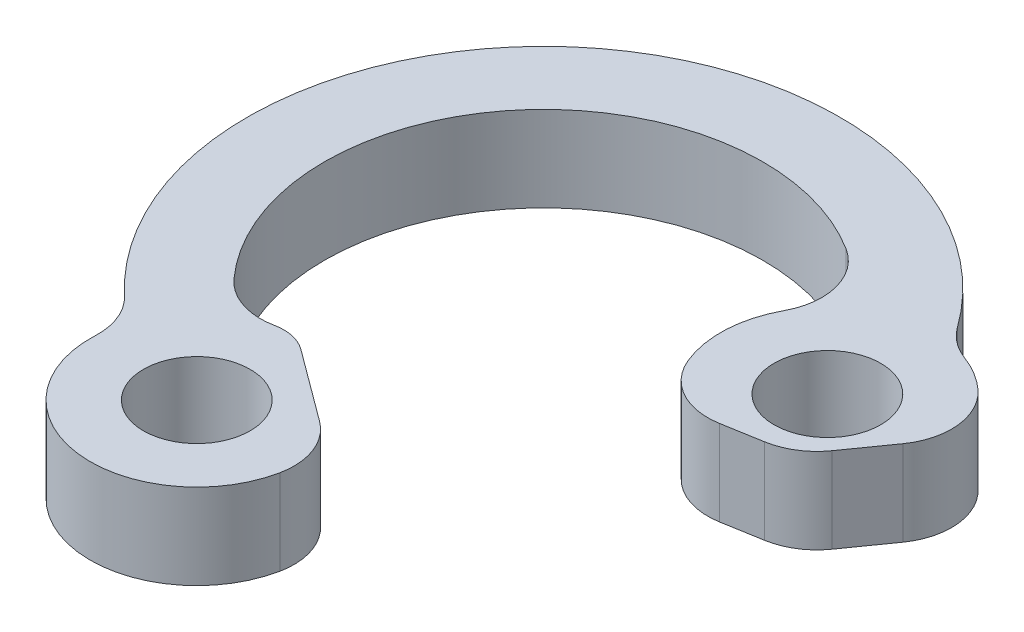
SolidWorks part; units mm, degrees
ref_plane "Front Plane" through (0, 0, 0) normal (0, 0, 1) x (1, 0, 0)
ref_plane "Top Plane" through (0, 0, 0) normal (0, 1, 0) x (1, 0, 0)
ref_plane "Right Plane" through (0, 0, 0) normal (1, 0, 0) x (0, 0, -1)
sketch "Sketch2" plane through (0, 0, 0) normal (0, 1, 0) x (1, 0, 0)
  circle A3 centre (87.0735, 81.0463) radius 2.5
  circle A5 centre (72.5387, 66.0204) radius 2.5
  arc A9 (84.158, 85.1082) -> (87.9596, 85.9672) centre (87.0735, 81.0463) ccw
  arc A10 (67.7859, 67.5732) -> (70.0824, 70.3755) centre (72.5387, 66.0204) ccw
  arc A16 (84.158, 85.1082) -> (70.0824, 70.3755) centre (76.1332, 78.6848) ccw
  arc A18 (87.9715, 85.965) -> (67.7859, 67.5732) centre (76.1332, 78.6848) ccw
extrude "Boss-Extrude1" add sketch "Sketch2" along normal blind 4 contours A18 A16 A3 A5 region at (68.387, 0, -86.0855)
fillet "Fillet1" radius 3 4 edges at (67.7859, 2, -67.5732) (70.0824, 2, -70.3755) (84.158, 2, -85.1082) (87.9715, 2, -85.965)
sketch "Sketch4" plane through (0, 0, 0) normal (0, -1, 0) x (-1, 0, 0)
  line L0 (-78.0637, 66.7167) -> (-72.145, 71.0915)
  line L1 (-72.145, 71.0915) -> (-73.0772, 72.3527)
  line L2 (-73.0772, 72.3527) -> (-78.9959, 67.9779)
  line L3 (-78.9959, 67.9779) -> (-78.0637, 66.7167)
extrude "Cut-Extrude2" cut sketch "Sketch4" against normal blind 7
fillet "Fillet2" radius 3 1 edges at (77.3948, 2, -67.211)
fillet "Fillet3" radius 2 1 edges at (72.2523, 2, -71.0122)
sketch "Sketch5" plane through (0, 4, 0) normal (0, 1, 0) x (1, 0, 0)
  line L0 (91.9157, 82.2928) -> (87.5095, 76.0653)
  line L1 (91.9157, 82.2928) -> (94.0459, 81.0848)
  line L2 (94.0459, 81.0848) -> (89.2486, 74.6155)
  line L3 (89.2486, 74.6155) -> (87.5095, 76.0653)
  arc A0 (82.6696, 83.4139) -> (88.8113, 85.7346) centre (87.0735, 81.0463) ccw construction
extrude "Cut-Extrude3" cut sketch "Sketch5" against normal blind 4
fillet "Fillet4" radius 3 2 edges at (87.5095, 2, -76.0653) (91.9157, 2, -82.2928)
sketch "Sketch6" plane through (0, 4, 0) normal (0, 1, 0) x (1, 0, 0)
  line L0 (88.77, 77.8469) -> (84.083, 77.0392)
  line L1 (90.8599, 80.8006) -> (88.5653, 77.5575) construction
  line L2 (84.083, 77.0392) -> (84.6593, 75.3461)
  line L3 (84.6593, 75.3461) -> (89.0906, 75.9868)
  line L4 (89.0906, 75.9868) -> (88.77, 77.8469)
  arc A0 (82.6696, 83.4139) -> (84.6804, 76.6562) centre (87.0735, 81.0463) ccw construction
extrude "Cut-Extrude4" cut sketch "Sketch6" against normal blind 5
fillet "Fillet5" radius 3 2 edges at (84.083, 2, -77.0392) (88.77, 2, -77.8469)
